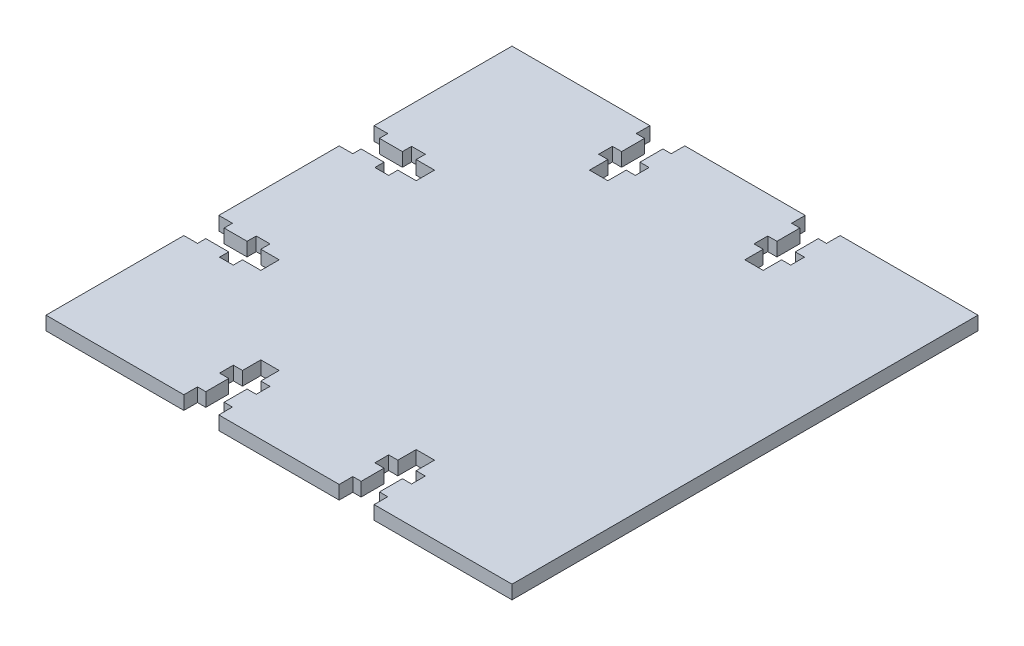
SolidWorks part; units mm, degrees
ref_plane "前视基准面" through (0, 0, 0) normal (0, 0, 1) x (1, 0, 0)
ref_plane "上视基准面" through (0, 0, 0) normal (0, 1, 0) x (1, 0, 0)
ref_plane "右视基准面" through (0, 0, 0) normal (1, 0, 0) x (0, 0, -1)
sketch "草图1" plane through (0, 0, 0) normal (0, 1, 0) x (1, 0, 0)
  line L0 (0, 50.8) -> (101.6, 50.8) construction
  line L1 (0, 0) -> (101.6, 0)
  line L2 (0, 0) -> (0, 101.6)
  line L3 (0, 101.6) -> (101.6, 101.6)
  line L4 (101.6, 0) -> (101.6, 101.6)
  line L5 (33.8667, 101.6) -> (33.8667, 0) construction
  line L6 (30.0567, 101.6) -> (30.0567, 98.6282)
  line L7 (30.0567, 98.6282) -> (31.8667, 98.6282)
  line L8 (31.8667, 98.6282) -> (31.8667, 93.6282)
  line L9 (31.8667, 93.6282) -> (29.8667, 93.6282)
  line L10 (29.8667, 93.6282) -> (29.8667, 90.6282)
  line L11 (29.8667, 90.6282) -> (31.8667, 90.6282)
  line L12 (31.8667, 90.6282) -> (31.8667, 86.6282)
  line L13 (31.8667, 86.6282) -> (35.8667, 86.6282)
  line L14 (37.8667, 90.6282) -> (35.8667, 90.6282)
  line L15 (35.8667, 90.6282) -> (35.8667, 86.6282)
  line L16 (37.8667, 93.6282) -> (37.8667, 90.6282)
  line L17 (35.8667, 93.6282) -> (37.8667, 93.6282)
  line L18 (35.8667, 98.6282) -> (35.8667, 93.6282)
  line L19 (37.6767, 98.6282) -> (35.8667, 98.6282)
  line L20 (37.6767, 101.6) -> (37.6767, 98.6282)
  line L21 (50.8, 101.6) -> (50.8, -1.3557) construction
  line L22 (101.6, 0) -> (0, 101.6) construction
  line L23 (0, 71.5433) -> (2.9718, 71.5433)
  line L24 (2.9718, 71.5433) -> (2.9718, 69.7333)
  line L25 (2.9718, 69.7333) -> (7.9718, 69.7333)
  line L26 (7.9718, 69.7333) -> (7.9718, 71.7333)
  line L27 (7.9718, 71.7333) -> (10.9718, 71.7333)
  line L28 (10.9718, 71.7333) -> (10.9718, 69.7333)
  line L29 (10.9718, 69.7333) -> (14.9718, 69.7333)
  line L30 (14.9718, 69.7333) -> (14.9718, 65.7333)
  line L31 (10.9718, 65.7333) -> (14.9718, 65.7333)
  line L32 (10.9718, 63.7333) -> (10.9718, 65.7333)
  line L33 (7.9718, 63.7333) -> (10.9718, 63.7333)
  line L34 (7.9718, 65.7333) -> (7.9718, 63.7333)
  line L35 (2.9718, 65.7333) -> (7.9718, 65.7333)
  line L36 (2.9718, 63.9233) -> (2.9718, 65.7333)
  line L37 (0, 63.9233) -> (2.9718, 63.9233)
  point P19 (33.8667, 86.6282)
  dimension "D1" = 101.6
  dimension "D2" = 101.6
  dimension "D3" = 33.8667
  dimension "D4" = 3.81
  dimension "D5" = 2
  dimension "D6" = 2.9718
  dimension "D7" = 5
  dimension "D8" = 3
  dimension "D9" = 2
  dimension "D10" = 2
  dimension "D11" = 4
extrude "凸台-拉伸1" add sketch "草图1" along normal blind 2.9718 contours L3 L20 L19 L18 L17 L16 L14 L15 L13 L12 L11 L10 L9 L8 L7 L6 L2 L1 L4 | L20 L3 L6 L7 L8 L9 L10 L11 L12 L13 L15 L14 L16 L17 L18 L19 | L2 L37 L36 L35 L34 L33 L32 L31 L30 L29 L28 L27 L26 L25 L24 L23 region at (51.2942, 0, -50.3058) region at (6.9932, 0, -67.7333) region at (33.8667, 0, -94.6068)
extrude "切除-拉伸1" cut sketch "草图1<3>" along normal through all contours L20 L3 L6 L7 L8 L9 L10 L11 L12 L13 L15 L14 L16 L17 L18 L19 region at (33.8667, 0, -94.6068)
sketch "草图1<3>" plane through (0, 0, 0) normal (0, 1, 0) x (1, 0, 0) same geometry as "草图1"
ref_plane "基准面1" through (0, 0, -50.8) normal (0, 0, -1) x (-1, 0, 0)
mirror "镜向1" about plane through (0, 0, -50.8) normal (0, 0, -1) of "切除-拉伸1"
ref_plane "基准面2" through (50.8, 0, 0) normal (1, 0, 0) x (0, 0, -1)
mirror "镜向2" about plane through (50.8, 0, 0) normal (1, 0, 0) of "镜向1", "切除-拉伸1"
extrude "切除-拉伸3" cut sketch "草图1<4>" along normal through all contours L2 L37 L36 L35 L34 L33 L32 L31 L30 L29 L28 L27 L26 L25 L24 L23 region at (6.9932, 0, -67.7333)
sketch "草图1<4>" plane through (0, 0, 0) normal (0, 1, 0) x (1, 0, 0) same geometry as "草图1"
mirror "镜向3" about plane through (0, 0, -50.8) normal (0, 0, -1) of "切除-拉伸3"
